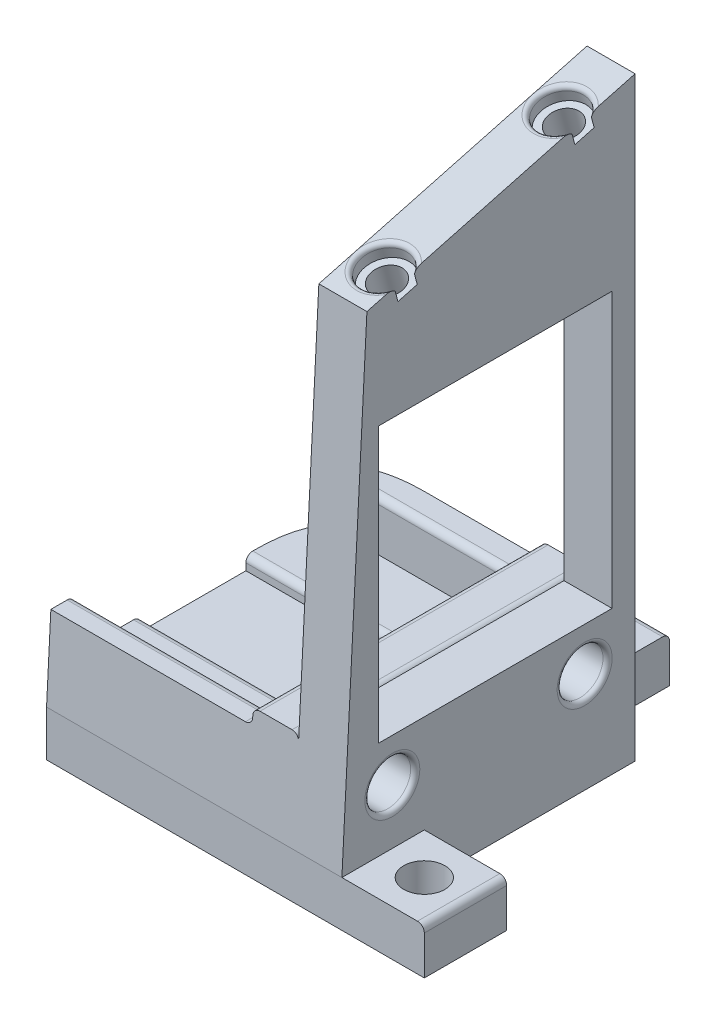
SolidWorks part; units mm, degrees
ref_plane "Front" through (0, 0, 0) normal (0, 0, 1) x (1, 0, 0)
ref_plane "Top" through (0, 0, 0) normal (0, 1, 0) x (1, 0, 0)
ref_plane "Right" through (0, 0, 0) normal (1, 0, 0) x (0, 0, -1)
sketch "Sketch1" plane through (0, 0, 0) normal (1, 0, 0) x (0, 0, -1)
  line L0 (-13.0089, 0) -> (13.0089, 0)
  line L1 (13.0089, 0) -> (13.0089, 8.5)
  line L2 (13.0089, 8.5) -> (5.7589, 8.5)
  line L3 (5.7589, 8.5) -> (5.7589, 7)
  line L4 (5.7589, 7) -> (-5.7589, 7)
  line L5 (-5.7589, 7) -> (-5.7589, 8.5)
  line L6 (-5.7589, 8.5) -> (-13.0089, 8.5)
  line L7 (-13.0089, 8.5) -> (-13.0089, 0)
  dimension "D1" = 8.5
  dimension "D2" = 7.25
  dimension "D3" = 26.0178
  dimension "D4" = 1.5
extrude "Boss-Extrude1" add sketch "Sketch1" along normal mid plane 22
sketch "Sketch3" plane through (0, 0, 0) normal (0, -1, 0) x (1, 0, 0)
  line L1 (-11, -13.0089) -> (11, -13.0089)
  line L2 (-11, -13.0089) -> (-11, -16.0089)
  line L3 (-11, -16.0089) -> (11, -16.0089)
  line L4 (11, -13.0089) -> (11, -16.0089)
  line L5 (-11, 13.0089) -> (11, 13.0089)
  line L6 (-11, 13.0089) -> (-11, 16.0089)
  line L7 (-11, 16.0089) -> (11, 16.0089)
  line L8 (11, 13.0089) -> (11, 16.0089)
  dimension "D1" = 3
  dimension "D2" = 22
  dimension "D3" = 3
  dimension "D4" = 22
extrude "Boss-Extrude2" add sketch "Sketch3" against normal blind 14
sketch "Sketch4" plane through (11, 0, 0) normal (1, 0, 0) x (0, 0, -1)
  line L0 (0, 0) -> (0, 15.7) construction
  line L1 (-16.0089, 0) -> (16.0089, 0) construction
  line L2 (-8.8, 15.7) -> (-16.0089, 15.7)
  line L3 (-16.0089, 14) -> (-16.0089, 0) construction
  line L4 (-16.0089, 15.7) -> (-16.0089, 0)
  line L5 (-16.0089, 0) -> (16.0089, 0)
  line L6 (16.0089, 0) -> (16.0089, 15.7)
  line L7 (16.0089, 14) -> (16.0089, 0) construction
  line L8 (16.0089, 15.7) -> (-8.8, 15.7)
  dimension "D2" = 15.7
extrude "Boss-Extrude3" add sketch "Sketch4" along normal blind 5
sketch "Sketch5" plane through (16, 0, 0) normal (1, 0, 0) x (0, 0, -1)
  line L0 (-16.0089, 11) -> (-10.5, 11) construction
  line L1 (-16.0089, 15.7) -> (-16.0089, 0) construction
  line L2 (-10.5, 11) -> (-10.5, 0) construction
  line L3 (-16.0089, 0) -> (16.0089, 0) construction
  line L4 (0, 0) -> (0, 15.7) construction
  line L5 (16.0089, 15.7) -> (-16.0089, 15.7) construction
  circle A0 centre (-10.5, 11) radius 1.75
  circle A1 centre (10.5, 11) radius 1.75
  dimension "D3" = 3.5
  dimension "D1" = 5.5089
  dimension "D2" = 11
extrude "Cut-Extrude1" cut sketch "Sketch5" against normal through all
sketch "Sketch6" plane through (0, 0, 0) normal (0, -1, 0) x (1, 0, 0)
  line L5 (16, -16.0089) -> (7, -16.0089)
  line L13 (16, -16.0089) -> (16, -25.0089)
  line L14 (16, -25.0089) -> (7, -25.0089)
  line L23 (7, -16.0089) -> (7, -25.0089)
  dimension "D1" = 9
  dimension "D2" = 9
extrude "Boss-Extrude4" add sketch "Sketch6" against normal blind 5
sketch "Sketch10" plane through (0, 0, 0) normal (0, -1, 0) x (1, 0, 0)
  line L1 (16, 16.0089) -> (16, -25.0089) construction
  line L2 (7, -25.0089) -> (16, -25.0089) construction
  line L3 (7, -25.0089) -> (7, -16.0089) construction
  line L4 (7, -16.0089) -> (16, -16.0089) construction
  line L5 (16, -25.0089) -> (16, -16.0089) construction
  line L7 (11.5, -20.5089) -> (7, -20.5089) construction
  line L9 (11.5, -20.5089) -> (11.5, -25.0089) construction
  circle A1 centre (11.5, -20.5089) radius 2.25
  dimension "D1" = 9
  dimension "D2" = 4.5
extrude "Cut-Extrude2" cut sketch "Sketch10" against normal through all
fillet "Fillet1" radius 0.75 11 edges at (0, 8.5, 5.7589) (0, 8.5, -5.7589) (11, 11.25, 13.0089) (11, 11.25, -13.0089) (0, 14, 13.0089) (0, 14, -13.0089) (11, 15.7, 0) (11, 14, 14.5089) (11, 14, -14.5089) (16, 15.7, 0) (11.5, 5, -25.0089)
fillet "Fillet2" radius 10 1 edges at (-11, 7, -16.0089) curvature continuous yes
sketch "Sketch11" plane through (16, 0, 0) normal (1, 0, 0) x (0, 0, -1)
  circle A0 centre (-10.5, 11) radius 2.5
  circle A1 centre (10.5, 11) radius 2.5
  dimension "D1" = 5
extrude "Cut-Extrude3" cut sketch "Sketch11" against normal blind 0.75
sketch "Sketch12" plane through (0, 0, 0) normal (0, -1, 0) x (1, 0, 0)
  line L0 (16, 16.0089) -> (16, -25.0089) construction
  line L1 (25, 16.0089) -> (16, 16.0089)
  line L2 (25, 16.0089) -> (25, -16.0089)
  line L3 (25, -16.0089) -> (16, -16.0089)
  line L4 (16, 16.0089) -> (16, -16.0089)
  line L5 (16, 16.0089) -> (-11, 16.0089) construction
  line L6 (-1, -16.0089) -> (7, -16.0089) construction
  dimension "D1" = 9
extrude "Boss-Extrude5" add sketch "Sketch12" against normal blind 65
sketch "Sketch13" plane through (25, 0, 0) normal (1, 0, 0) x (0, 0, -1)
  line L7 (16.0089, 65) -> (-16.0089, 56.4209)
  line L8 (-16.0089, 65) -> (-16.0089, 0) construction
  line L9 (-16.0089, 56.4209) -> (-16.0089, 65)
  line L10 (-16.0089, 65) -> (16.0089, 65)
  dimension "D1" = 15
extrude "Cut-Extrude4" cut sketch "Sketch13" against normal up to surface (9 mm away) up to face at (16, 39.975, 0)
sketch "Sketch14" plane through (25, 0, 0) normal (1, 0, 0) x (0, 0, -1)
  circle A0 centre (10.5, 11) radius 2.5
  circle A1 centre (-10.5, 11) radius 2.5
  dimension "D1" = 5
extrude "Cut-Extrude5" cut sketch "Sketch14" against normal up to surface (9.75 mm away) up to face at (15.25, 11, 8)
sketch "Sketch15" plane through (0, 56.6436, 15.1776) normal (0, 0.9659, 0.2588) x (1, 0, 0)
  line L0 (19, 6.1394) -> (19, 26.1394) construction
  line L1 (19, 6.1394) -> (19, -0.8606) construction
  line L2 (16, -0.8606) -> (25, -0.8606) construction
  line L3 (19, 6.1394) -> (25, 6.1394) construction
  line L4 (16, -0.8606) -> (16, 32.2866) construction
  line L5 (25, -0.8606) -> (25, 32.2866) construction
  circle A0 centre (19, 6.1394) radius 1.7
  circle A1 centre (19, 26.1394) radius 1.7
  dimension "D1" = 3.4
  dimension "D3" = 3
  dimension "D2" = 20
  dimension "D4" = 7
extrude "Cut-Extrude6" cut sketch "Sketch15" against normal blind 5
sketch "Sketch16" plane through (0, 56.6436, 15.1776) normal (0, 0.9659, 0.2588) x (1, 0, 0)
  circle A0 centre (19, 26.1394) radius 2.5
  circle A1 centre (19, 6.1394) radius 2.5
  dimension "D1" = 5
extrude "Cut-Extrude7" cut sketch "Sketch16" against normal blind 1.6
fillet "Fillet3" radius 0.5 2 edges at (19, 62.7619, -7.6563) (19, 57.5855, 11.6622)
fillet "Fillet4" radius 0.5 2 edges at (25, 11, -13) (25, 11, 8)
ref_plane "Plane2" through (0, 65, 0) normal (0, -1, 0) x (-1, 0, 0)
sketch "Sketch18" plane through (0, 65, 0) normal (0, -1, 0) x (-1, 0, 0)
  line L0 (-16, -16.0089) -> (-25, -16.0089) construction
  line L1 (-25, 16.0089) -> (-21.25, 16.0089)
  line L2 (-25, 16.0089) -> (-25, -16.0089)
  line L3 (-25, -16.0089) -> (-21.25, -16.0089)
  line L4 (-21.25, 16.0089) -> (-21.25, -16.0089)
  dimension "D1" = 3.75
extrude "Cut-Extrude8" cut sketch "Sketch18" along normal through all
fillet "Fillet5" radius 0.5 2 edges at (21.25, 11, -13) (21.25, 11, 8)
sketch "Sketch19" plane through (0, 0, 0) normal (0, -1, 0) x (1, 0, 0)
  line L1 (21.25, 16.0089) -> (30.25, 16.0089)
  line L2 (21.25, 16.0089) -> (21.25, 7.0089)
  line L3 (21.25, 7.0089) -> (30.25, 7.0089)
  line L4 (30.25, 16.0089) -> (30.25, 7.0089)
  dimension "D1" = 9
  dimension "D2" = 9
extrude "Boss-Extrude6" add sketch "Sketch19" against normal blind 5
sketch "Sketch20" plane through (0, 5, 0) normal (0, 1, 0) x (1, 0, 0)
  line L0 (25.75, -11.5089) -> (21.25, -11.5089) construction
  line L1 (21.25, -16.0089) -> (21.25, -7.0089) construction
  line L2 (25.75, -11.5089) -> (25.75, -7.0089) construction
  line L3 (21.25, -7.0089) -> (30.25, -7.0089) construction
  circle A0 centre (25.75, -11.5089) radius 2.25
  dimension "D1" = 4.5
extrude "Cut-Extrude9" cut sketch "Sketch20" against normal up to next
fillet "Fillet6" radius 0.75 1 edges at (30.25, 5, 11.5089)
sketch "Sketch21" plane through (16, 0, 0) normal (-1, 0, 0) x (0, 0, 1)
  line L0 (-16.0089, 15.7) -> (16.0089, 15.7) construction
  line L1 (12.0089, 15.7) -> (-13.4911, 15.7)
  line L2 (12.0089, 15.7) -> (12.0089, 45.7)
  line L3 (12.0089, 45.7) -> (-13.4911, 45.7)
  line L4 (-13.4911, 15.7) -> (-13.4911, 45.7)
  line L7 (16.0089, 56.4209) -> (16.0089, 14.95) construction
  dimension "D1" = 4
  dimension "D2" = 25.5
  dimension "D3" = 30
extrude "Cut-Extrude10" cut sketch "Sketch21" against normal up to next
sketch "Sketch22" plane through (21.25, 0, 0) normal (1, 0, 0) x (0, 0, -1)
  line L0 (-16.0089, 56.4209) -> (-16.0089, 5)
  line L1 (-16.0089, 5) -> (-13.2757, 57.1532)
  line L2 (-11.1641, 57.719) -> (-16.0089, 56.4209) construction
  line L3 (-13.2757, 57.1532) -> (-16.0089, 56.4209)
  dimension "D1" = 3
extrude "Cut-Extrude11" cut sketch "Sketch22" against normal through all
